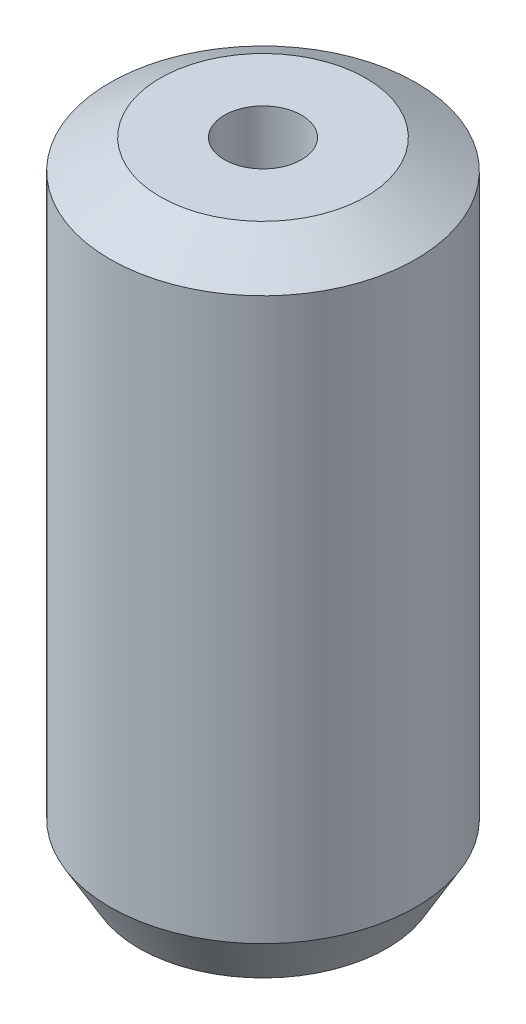
SolidWorks part; units mm, degrees
ref_plane "Front Plane" through (0, 0, 0) normal (0, 0, 1) x (1, 0, 0)
ref_plane "Top Plane" through (0, 0, 0) normal (0, 1, 0) x (1, 0, 0)
ref_plane "Right Plane" through (0, 0, 0) normal (1, 0, 0) x (0, 0, -1)
sketch "Sketch1" plane through (0, 0, 0) normal (0, 1, 0) x (1, 0, 0)
  circle A0 centre (0, 0) radius 10
  dimension "SHAFT_OD" = 20
extrude "Boss-Extrude1" add sketch "Sketch1" along normal blind 41.8461
sketch "Sketch2" plane through (0, 0, 0) normal (0, 1, 0) x (1, 0, 0)
  circle A0 centre (0, 0) radius 2.5231
  dimension "BORE_D" = 5.0461
extrude "Cut-Extrude1" cut sketch "Sketch2" along normal through all
chamfer "Chamfer1" distance 1.8941 angle 60 2 edges at (0, 41.8461, 10) (0, 0, 10) first distance on face at (0, 41.8461, 10) first distance on face at (0, 0, 2.5231)
